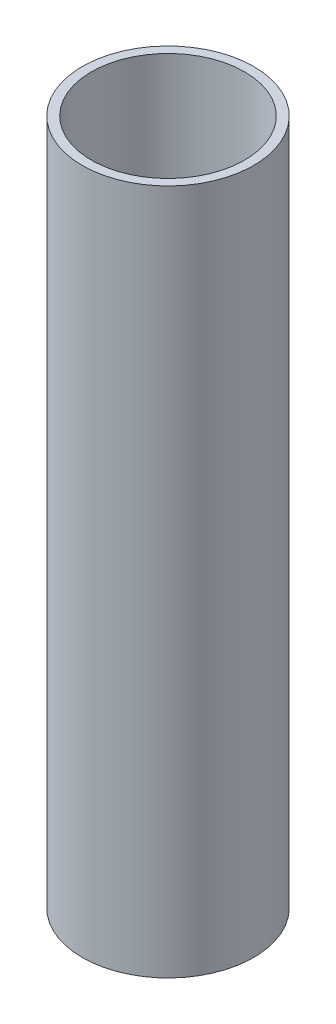
SolidWorks part; units mm, degrees
material "AISI Type 316L stainless steel"
ref_plane "Front Plane" through (0, 0, 0) normal (0, 0, 1) x (1, 0, 0)
ref_plane "Top Plane" through (0, 0, 0) normal (0, 1, 0) x (1, 0, 0)
ref_plane "Right Plane" through (0, 0, 0) normal (1, 0, 0) x (0, 0, -1)
sketch "Sketch1" plane through (0, 0, 0) normal (0, 1, 0) x (1, 0, 0)
  circle A0 centre (0, 0) radius 4.7625
  circle A1 centre (0, 0) radius 4.2545
  dimension "D1" = 9.525
  dimension "D2" = 0.508
extrude "Boss-Extrude1" add sketch "Sketch1" along normal blind 38.1
